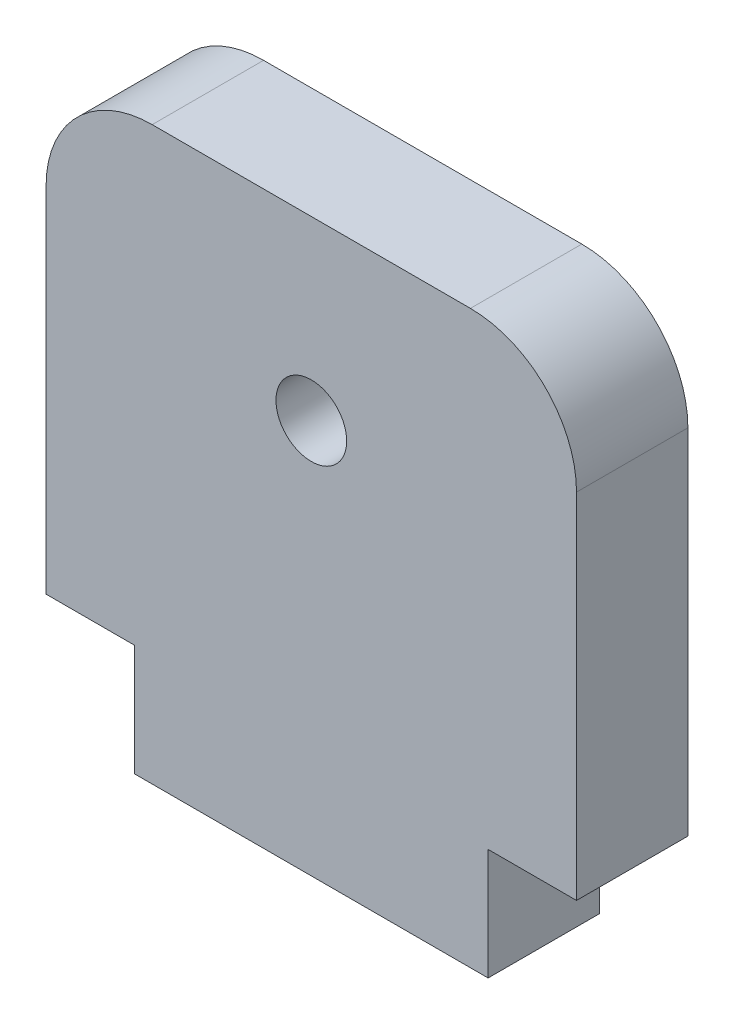
SolidWorks part; units mm, degrees
material "Hexcel AS4C (3000 Filaments)"
ref_plane "Front Plane" through (0, 0, 0) normal (0, 0, 1) x (1, 0, 0)
ref_plane "Top Plane" through (0, 0, 0) normal (0, 1, 0) x (1, 0, 0)
ref_plane "Right Plane" through (0, 0, 0) normal (1, 0, 0) x (0, 0, -1)
sketch "Sketch2" plane through (0, 0, 0) normal (0, 0, 1) x (1, 0, 0)
  line L0 (-9.525, -8.255) -> (-6.35, -8.255)
  line L1 (-9.525, -8.255) -> (9.525, -8.255) construction
  line L2 (-9.525, -8.255) -> (-9.525, 4.445)
  line L3 (-5.715, 8.255) -> (5.715, 8.255)
  line L4 (9.525, -8.255) -> (9.525, 4.445)
  line L5 (-9.525, -8.255) -> (9.525, 8.255) construction
  line L6 (-9.525, 8.255) -> (9.525, -8.255) construction
  line L7 (-6.35, -8.255) -> (-6.35, -12.255)
  line L8 (-6.35, -12.255) -> (6.35, -12.255)
  line L9 (6.35, -12.255) -> (6.35, -8.255)
  line L10 (6.35, -8.255) -> (9.525, -8.255)
  arc A1 (5.715, 8.255) -> (9.525, 4.445) centre (5.715, 4.445) cw
  arc A2 (-9.525, 4.445) -> (-5.715, 8.255) centre (-5.715, 4.445) cw
  circle A3 centre (0, 1.905) radius 1.27
  point P0 (0, 0)
  point P18 (0, 0)
  point P19 (0, 8.255)
  dimension "D3" = 2.54
  dimension "D6" = 3.81
  dimension "D1" = 16.51
  dimension "D2" = 19.05
  dimension "D4" = 4
  dimension "D5" = 12.7
  dimension "D7" = 6.35
extrude "Boss-Extrude1" add sketch "Sketch2" along normal blind 4
